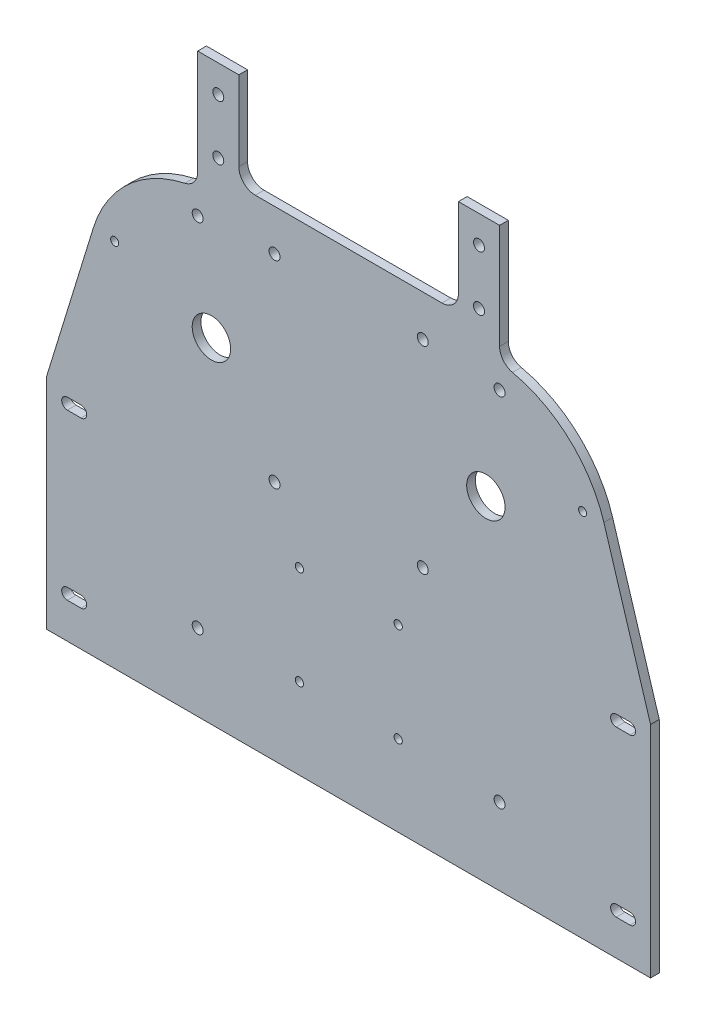
SolidWorks part; units mm, degrees
ref_plane "Front Plane" through (0, 0, 0) normal (0, 0, 1) x (1, 0, 0)
ref_plane "Top Plane" through (0, 0, 0) normal (0, 1, 0) x (1, 0, 0)
ref_plane "Right Plane" through (0, 0, 0) normal (1, 0, 0) x (0, 0, -1)
sketch "Sketch1" plane through (0, 0, 0) normal (0, 0, 1) x (1, 0, 0)
  line L1 (-100, -75) -> (100, -75)
  line L2 (-100, -75) -> (-100, 75)
  line L3 (-100, 75) -> (100, 75)
  line L4 (100, -75) -> (100, 75)
  line L5 (-100, -75) -> (100, 75) construction
  line L6 (-100, 75) -> (100, -75) construction
  line L8 (-47.5, 40) -> (47.5, 40) construction
  line L9 (0, 75) -> (0, -75) construction
  line L10 (-27, -52) -> (27, -52) construction
  line L11 (-27, -52) -> (-27, 20) construction
  line L12 (-27, 20) -> (27, 20) construction
  line L13 (27, -52) -> (27, 20) construction
  line L14 (-27, -52) -> (27, 20) construction
  line L15 (-27, 20) -> (27, -52) construction
  line L23 (-55, 70) -> (55, 70)
  line L24 (-55, 70) -> (-55, -70)
  line L25 (-55, -70) -> (55, -70)
  line L26 (55, 70) -> (55, -70)
  line L27 (-55, 70) -> (55, -70) construction
  line L28 (-55, -70) -> (55, 70) construction
  line L29 (-40, 70) -> (40, 70)
  line L30 (-40, 70) -> (-40, 35)
  line L31 (-40, 35) -> (40, 35)
  line L32 (40, 70) -> (40, 35)
  line L33 (-40, 70) -> (40, 35) construction
  line L34 (-40, 35) -> (40, 70) construction
  circle A2 centre (-47.5, 40) radius 2
  circle A3 centre (47.5, 40) radius 2
  circle A4 centre (-27, 20) radius 2
  circle A5 centre (27, 20) radius 2
  circle A6 centre (27, -52) radius 2
  circle A7 centre (-27, -52) radius 2
  circle A8 centre (-47.5, 60) radius 2
  circle A9 centre (47.5, 60) radius 2
  point P0 (0, 0)
  point P15 (0, 40)
  point P18 (0, -16)
  point P56 (0, 0)
  point P63 (0, 52.5)
  dimension "D3" = 4
  dimension "D4" = 20
  dimension "D5" = 4
  dimension "D8" = 4
  dimension "D1" = 150
  dimension "D2" = 200
  dimension "D6" = 72
  dimension "D7" = 54
  dimension "D14" = 30
  dimension "D15" = 140
  dimension "D16" = 110
  dimension "D17" = 95
  dimension "D18" = 20
  dimension "D19" = 35
  dimension "D20" = 80
extrude "Boss-Extrude1" add sketch "Sketch1" along normal blind 3.175 contours L23 L32 L31 L30 L24 L25 L26 A7 A6 A5 A4 A3 A2 region at (0, -11.8972, 0)
sketch "Sketch3" plane through (0, 0, 3.175) normal (0, 0, 1) x (1, 0, 0)
  line L0 (0, 0) -> (0, 95.843) construction
  line L1 (-50, -18) -> (-85.2385, -5.1742) construction
  line L2 (-50, -18) -> (-56.5118, 18.9303) construction
  line L3 (-50, -18) -> (-87.5, -18) construction
  circle A0 centre (-50, -18) radius 30 construction
  circle A1 centre (-50, -18) radius 45
  circle A2 centre (-50, -18) radius 37.5 construction
  circle A3 centre (-85.2385, -5.1742) radius 1.4732
  circle A5 centre (-47.5, 40) radius 2 construction
  circle A7 centre (85.2385, -5.1742) radius 1.4732
  circle A8 centre (50, -18) radius 45
  line M5 (-55, -70) -> (55, -70)
  line M11 (55, -70) -> (55, 70)
  line M13 (40, 70) -> (40, 35)
  line M14 (40, 35) -> (-40, 35)
  line M15 (-40, 35) -> (-40, 70)
  line M17 (-55, 70) -> (-55, -70)
  circle M23 centre (-47.5, 40) radius 2
  circle M24 centre (47.5, 40) radius 2
  circle M25 centre (-27, 20) radius 2
  circle M26 centre (27, 20) radius 2
  circle M27 centre (27, -52) radius 2
  circle M28 centre (-27, -52) radius 2
  dimension "D1" = 60
  dimension "D3" = 7.5
  dimension "D4" = 58
  dimension "D5" = 20
  dimension "D6" = 80
  dimension "D7" = 100
  dimension "D2" = 15
extrude "Boss-Extrude3" add sketch "Sketch3" against normal up to surface (3.175 mm away) contours A1 A3 M17 | A1 M15 M17 M5 M14 M28 M25 M23 | A8 M11 M13 M14 M5 M27 M26 M24 | A8 A7 M11 region at (-33.6109, -17.9702, 3.175) region at (33.6109, -17.9702, 3.175) region at (71.7941, -18.0321, 3.175) region at (-71.7941, -18.0321, 3.175) up to face at (0, 26.25, 0)
sketch "Sketch4" plane through (0, 0, 3.175) normal (0, 0, 1) x (1, 0, 0)
  line L1 (-60, -130) -> (-111.1989, -130)
  line L2 (-60, -130) -> (-60, -60)
  line L3 (-60, -60) -> (-89.0752, -60)
  line L4 (-110, -130) -> (-110, -60)
  line L5 (-60, -130) -> (-110, -60) construction
  line L6 (-60, -60) -> (-110, -130) construction
  line L10 (-111.1989, -130) -> (-110, -130)
  line L11 (-110, -60) -> (-93.0112, -4.7698)
  line L12 (-89.0752, -60) -> (-84.8958, -46.4128)
  line L13 (-89.0752, -60) -> (-110, -60) construction
  line L14 (-110, -95) -> (-60, -95) construction
  line L15 (-100, -60) -> (-100, -95) construction
  line L18 (-60, -130) -> (-60, -122.95)
  line L22 (-60, -60) -> (25, -60)
  line L23 (-97.5, -65) -> (-102.5, -65) construction
  line L24 (-97.5, -67.05) -> (-102.5, -67.05)
  line L25 (-97.5, -62.95) -> (-102.5, -62.95)
  line L26 (-97.5, -125) -> (-102.5, -125) construction
  line L27 (-97.5, -122.95) -> (-102.5, -122.95)
  line L28 (-97.5, -127.05) -> (-102.5, -127.05)
  line L29 (-60, -60) -> (-60, -130)
  line L30 (-60, -130) -> (25, -130)
  line L31 (25, -60) -> (25, -130)
  line L32 (-60, -60) -> (25, -130) construction
  line L33 (-60, -130) -> (25, -60) construction
  line L34 (25, -130) -> (-110, -130)
  line L35 (25, -130) -> (25, -140)
  line L36 (25, -140) -> (-110, -140)
  line L37 (-110, -130) -> (-110, -140)
  line L38 (25, -130) -> (-110, -140) construction
  line L39 (25, -140) -> (-110, -130) construction
  arc A2 (-55, 26.7214) -> (-55, -62.7214) centre (-50, -18) ccw construction
  arc A3 (-84.8958, -46.4128) -> (-93.0112, -4.7698) centre (-50, -18) cw
  circle A4 centre (-100, -65) radius 2.05 construction
  circle A6 centre (-100, -125) radius 2.05 construction
  arc A7 (-97.5, -67.05) -> (-97.5, -62.95) centre (-97.5, -65) ccw
  arc A8 (-102.5, -62.95) -> (-102.5, -67.05) centre (-102.5, -65) ccw
  arc A9 (-97.5, -122.95) -> (-97.5, -127.05) centre (-97.5, -125) cw
  arc A10 (-102.5, -127.05) -> (-102.5, -122.95) centre (-102.5, -125) cw
  point P0 (-85, -95)
  point P15 (-42.5, -135)
  point P31 (-17.5, -95)
  point P36 (-87.5, -107.6256)
  point P38 (-100, -65)
  point P48 (-100, -125)
  arc M14 (-55, 26.7214) -> (-55, -62.7214) centre (-50, -18) ccw
  line M20 (-55, -70) -> (55, -70)
  line M84 (-55, -62.7214) -> (-55, -70)
  dimension "D7" = 4.1
  dimension "D9" = 2.05
  dimension "D1" = 60
  dimension "D2" = 60
  dimension "D3" = 50
  dimension "D4" = 70
  dimension "D5" = 10
  dimension "D6" = 20
  dimension "D8" = 10
  dimension "D10" = 5
  dimension "D11" = 5
extrude "Boss-Extrude4" add sketch "Sketch4" against normal up to surface (3.175 mm away) contours L11 L4 A8 L25 A7 L24 L28 A10 L27 A9 M14 | L12 L3 M14 | L31 L2 L30 M20 M84 M14 | L10 L37 L36 L35 L30 L1 region at (-42.5, -135, 3.175) region at (-86.4828, -87.8935, 3.175) region at (-17.7982, -99.748, 3.175) region at (-80.7795, -55.7852, 3.175) up to face at (-25, 20, 0)
mirror "Mirror2" about plane through (0, 0, 0) normal (1, 0, 0) of "Boss-Extrude4"
fillet "Fillet1" radius 6 4 edges at (-55, 26.7214, 1.5875) (-40, 35, 1.5875) (40, 35, 1.5875) (55, 26.7214, 1.5875)
sketch "Sketch5" plane through (0, 0, 3.175) normal (0, 0, 1) x (1, 0, 0)
  circle A0 centre (-50, -18) radius 7
  circle A1 centre (50, -18) radius 7
  circle A5 centre (-50, -18) radius 45
  circle A6 centre (-50, -18) radius 45 construction
  circle A7 centre (50, -18) radius 45
  circle A8 centre (50, -18) radius 45 construction
  dimension "D1" = 14
  dimension "D3" = 0
  dimension "D4" = 0
extrude "Cut-Extrude1" cut sketch "Sketch5" against normal blind 10
sketch "Sketch6" plane through (0, 0, 3.175) normal (0, 0, 1) x (1, 0, 0)
  line L1 (-30, -72) -> (30, -72) construction
  line L2 (-30, -72) -> (-30, -113) construction
  line L3 (-30, -113) -> (30, -113) construction
  line L4 (30, -72) -> (30, -113) construction
  line L5 (-30, -72) -> (30, -113) construction
  line L6 (-30, -113) -> (30, -72) construction
  line L7 (-17.94, -74.5) -> (18.06, -74.5) construction
  line L8 (-17.94, -74.5) -> (-17.94, -110.5) construction
  line L9 (-17.94, -110.5) -> (18.06, -110.5) construction
  line L10 (18.06, -74.5) -> (18.06, -110.5) construction
  line L11 (-17.94, -74.5) -> (18.06, -110.5) construction
  line L12 (-17.94, -110.5) -> (18.06, -74.5) construction
  circle A0 centre (-17.94, -110.5) radius 1.5
  circle A1 centre (-17.94, -74.5) radius 1.5
  circle A2 centre (18.06, -74.5) radius 1.5
  circle A3 centre (18.06, -110.5) radius 1.5
  circle A4 centre (-27, -52) radius 2 construction
  point P4 (0, -92.5)
  point P9 (0.06, -92.5)
  dimension "D3" = 3
  dimension "D1" = 41
  dimension "D2" = 60
  dimension "D4" = 36
  dimension "D5" = 36
  dimension "D6" = 12.06
  dimension "D7" = 2.5
  dimension "D8" = 20
extrude "Cut-Extrude2" cut sketch "Sketch6" against normal blind 10
sketch "Sketch7" plane through (0, 0, 3.175) normal (0, 0, 1) x (1, 0, 0)
  line L1 (-55, 18) -> (55, 18) construction
  line L2 (-55, 18) -> (-55, -112) construction
  line L3 (-55, -112) -> (55, -112) construction
  line L4 (55, 18) -> (55, -112) construction
  line L5 (-55, 18) -> (55, -112) construction
  line L6 (-55, -112) -> (55, 18) construction
  circle A0 centre (-55, 18) radius 2
  circle A1 centre (55, 18) radius 2
  circle A2 centre (55, -112) radius 2
  circle A3 centre (-55, -112) radius 2
  circle A5 centre (-17.94, -74.5) radius 1.5 construction
  point P4 (0, -47)
  dimension "D1" = 4
  dimension "D3" = 37.5
  dimension "D2" = 130
  dimension "D4" = 110
extrude "Cut-Extrude3" cut sketch "Sketch7" against normal blind 10
